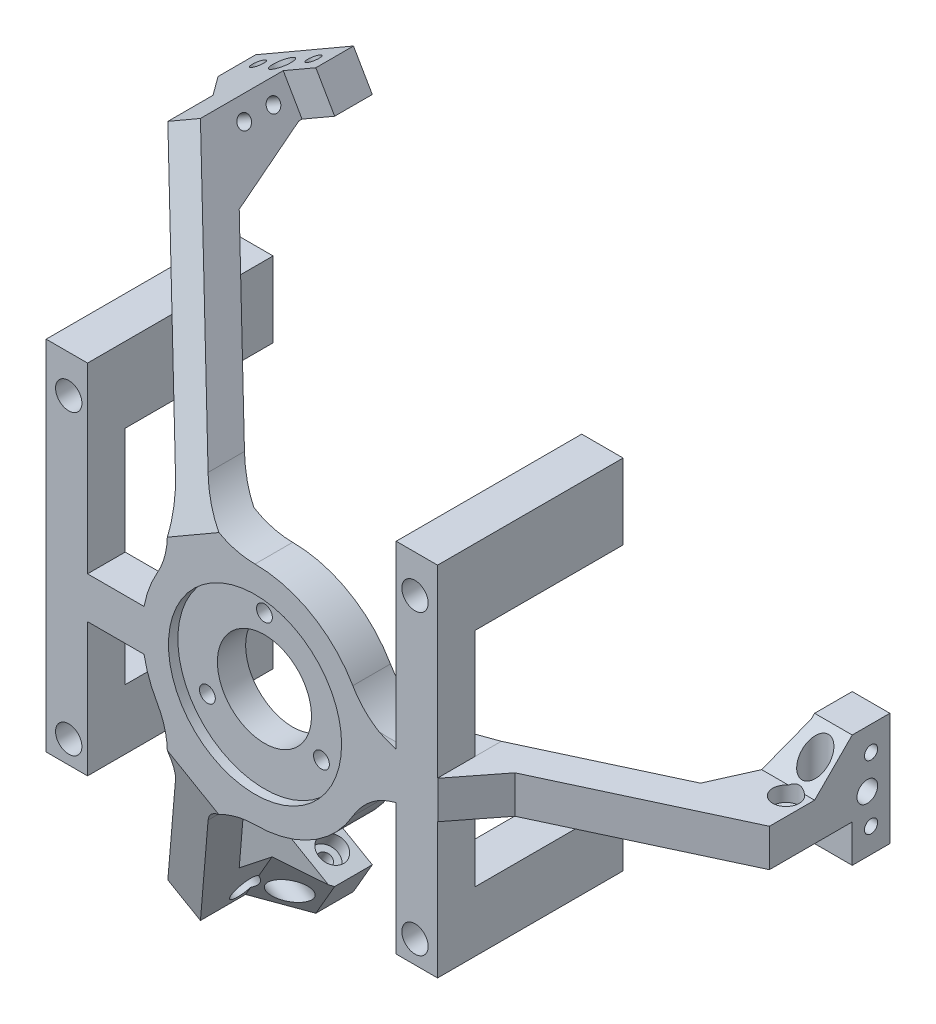
SolidWorks part; units mm, degrees
ref_plane "Plan de face" through (0, 0, 0) normal (0, 0, 1) x (1, 0, 0)
ref_plane "Plan de dessus" through (0, 0, 0) normal (0, 1, 0) x (1, 0, 0)
ref_plane "Plan de droite" through (0, 0, 0) normal (1, 0, 0) x (0, 0, -1)
sketch "Esquisse1" plane through (0, 0, 0) normal (0, 0, 1) x (1, 0, 0)
  line L0 (0, 0) -> (93.67, 0) construction
  line L1 (93.67, 15) -> (103.67, 15)
  line L2 (93.67, 15) -> (93.67, -15)
  line L3 (93.67, -15) -> (103.67, -15)
  line L4 (103.67, 15) -> (103.67, -15)
  line L5 (-33.8446, -88.6206) -> (-59.8254, -73.6206)
  line L6 (-33.8446, -88.6206) -> (-38.8446, -97.2809)
  line L7 (-38.8446, -97.2809) -> (-64.8254, -82.2809)
  line L8 (-59.8254, -73.6206) -> (-64.8254, -82.2809)
  line L9 (-59.8254, 73.6206) -> (-33.8446, 88.6206)
  line L10 (-59.8254, 73.6206) -> (-64.8254, 82.2809)
  line L11 (-64.8254, 82.2809) -> (-38.8446, 97.2809)
  line L12 (-33.8446, 88.6206) -> (-38.8446, 97.2809)
  point P17 (0, 0)
  dimension "D1" = 30
  dimension "D2" = 10
  dimension "D3" = 93.67
  dimension "D4" = 3
extrude "Boss.-Extru.1" add sketch "Esquisse1" along normal blind 10
sketch "Esquisse2" plane through (0, 0, 10) normal (0, 0, 1) x (1, 0, 0)
  line L0 (-57.0272, 86.7831) -> (-46.3532, 92.9458)
  line L1 (-38.8446, 97.2809) -> (-64.8254, 82.2809) construction
  line L2 (93.67, 15) -> (93.67, -15) construction
  line L3 (93.67, 5) -> (103.67, 5)
  line L4 (93.67, 5) -> (93.67, -5)
  line L5 (93.67, -5) -> (103.67, -5)
  line L6 (103.67, 5) -> (103.67, -5)
  line L7 (103.67, -15) -> (103.67, 15) construction
  line L8 (-42.5049, -83.6206) -> (-51.1651, -78.6206)
  line L9 (-42.5049, -83.6206) -> (-47.5049, -92.2809)
  line L10 (-47.5049, -92.2809) -> (-56.1651, -87.2809)
  line L11 (-51.1651, -78.6206) -> (-56.1651, -87.2809)
  line L12 (-51.1651, 78.6206) -> (-42.5049, 83.6206)
  line L13 (-51.1651, 78.6206) -> (-56.1651, 87.2809)
  line L14 (-56.1651, 87.2809) -> (-47.5049, 92.2809)
  line L15 (-42.5049, 83.6206) -> (-47.5049, 92.2809)
  point P12 (93.67, 0)
  point P13 (93.67, 0)
  point P24 (0, 0)
  line M6 (-59.8254, 73.6206) -> (-33.8446, 88.6206)
  dimension "D1" = 3
extrude "Boss.-Extru.2" add sketch "Esquisse2" along normal blind 45 contours L15 L0 L13 M6 | L6 L3 L4 L5 | L8 L11 L10 L9 region at (-49.335, 85.4507, 10) region at (98.67, 0, 10) region at (-49.335, -85.4507, 10)
sketch "Esquisse3" plane through (0, 0, 55) normal (0, 0, 1) x (1, 0, 0)
  line L0 (103.67, 5) -> (103.67, -5) construction
  line L1 (-47.5049, -92.2809) -> (-56.1651, -87.2809) construction
  line L2 (-47.5049, 92.2809) -> (-56.1651, 87.2809) construction
  line L3 (103.67, 5) -> (103.67, -5)
  line L4 (-47.5049, -92.2809) -> (-56.1651, -87.2809)
  line L5 (-47.5049, 92.2809) -> (-56.1651, 87.2809)
  line L6 (-56.1651, -87.2809) -> (-19.1203, -23.1174)
  line L7 (-47.5049, -92.2809) -> (-10.4601, -28.1174)
  line L8 (103.67, -5) -> (29.5804, -5)
  line L9 (103.67, 5) -> (29.5804, 5)
  line L10 (-56.1651, 87.2809) -> (-19.1203, 23.1174)
  line L11 (-47.5049, 92.2809) -> (-10.4601, 28.1174)
  line L12 (-51.1651, -78.6206) -> (-56.1651, -87.2809) construction
  line L13 (-42.5049, -83.6206) -> (-47.5049, -92.2809) construction
  line L14 (93.67, -5) -> (103.67, -5) construction
  line L15 (93.67, 5) -> (103.67, 5) construction
  line L16 (-51.1651, 78.6206) -> (-56.1651, 87.2809) construction
  line L17 (-42.5049, 83.6206) -> (-47.5049, 92.2809) construction
  arc A0 (-19.1203, -23.1174) -> (-19.1203, 23.1174) centre (0, 0) cw
  arc A1 (-10.4601, 28.1174) -> (29.5804, 5) centre (0, 0) cw
  arc A2 (29.5804, -5) -> (-10.4601, -28.1174) centre (0, 0) cw
  dimension "D1" = 30
extrude "Boss.-Extru.3" add sketch "Esquisse3" along normal blind 10
chamfer "Chanfrein1" distance 28 angle 65 3 edges at (93.67, 0, 55) (-46.835, -81.1206, 55) (-46.835, 81.1206, 55) first distance on face at (93.67, 0, 18.75) first distance on face at (-46.835, -81.1206, 18.75) first distance on face at (-46.835, 81.1206, 18.75)
chamfer "Chanfrein2" distance 33 angle 65 3 edges at (-51.835, -89.7809, 65) (-51.835, 89.7809, 65) (103.67, 0, 65) first distance on face at (-51.835, -89.7809, 21.25) first distance on face at (-51.835, 89.7809, 21.25) first distance on face at (103.67, 0, 21.25)
fillet "Congé1" radius 20 6 edges at (29.5804, -5, 60) (-10.4601, -28.1174, 60) (-19.1203, -23.1174, 60) (-19.1203, 23.1174, 60) (29.5804, 5, 60) (-10.4601, 28.1174, 60)
chamfer "Chanfrein3" distance 10 angle 41 3 edges at (-46.835, 81.1206, 27) (-46.835, -81.1206, 27) (93.67, 0, 27) first distance on face at (-28.4061, 49.2008, 44.1871) first distance on face at (-28.4061, -49.2008, 44.1871) first distance on face at (56.8122, 0, 44.1871)
sketch "Esquisse4" plane through (0, 0, 65) normal (0, 0, 1) x (1, 0, 0)
  circle A0 centre (0, 0) radius 12.5
  dimension "D1" = 25
extrude "Enlèv. mat.-Extru.1" cut sketch "Esquisse4" against normal up to next
sketch "Esquisse5" plane through (0, 0, 65) normal (0, 0, 1) x (1, 0, 0)
  circle A0 centre (0, 0) radius 23
  dimension "D1" = 46
extrude "Enlèv. mat.-Extru.2" cut sketch "Esquisse5" against normal blind 2.5
sketch "Esquisse6" plane through (0, 0, 62.5) normal (0, 0, 1) x (1, 0, 0)
  line L0 (0, 17.5) -> (0, 0) construction
  circle A0 centre (0, 17.5) radius 2.1
  circle A1 centre (15.1554, -8.75) radius 2.1
  circle A2 centre (-15.1554, -8.75) radius 2.1
  point P10 (0, 0)
  dimension "D2" = 4.2
  dimension "D1" = 17.5
  dimension "D3" = 3
extrude "Enlèv. mat.-Extru.3" cut sketch "Esquisse6" against normal up to next
sketch "Esquisse7" plane through (0, 0, 55) normal (0, 0, -1) x (-1, 0, 0)
  line L0 (0, 0) -> (44.5, 0) construction
  line L1 (-37.5, -41) -> (-48.5, -41)
  line L2 (-37.5, -41) -> (-37.5, 54)
  line L3 (-37.5, 54) -> (-48.5, 54)
  line L4 (-48.5, -41) -> (-48.5, 54)
  line L5 (55.5, -41) -> (44.5, -41)
  line L6 (44.5, -41) -> (44.5, -5.5)
  line L7 (44.5, -5.5) -> (29.4915, -5.5)
  line L8 (55.5, -41) -> (55.5, 54)
  line L9 (55.5, 54) -> (44.5, 54)
  line L10 (44.5, 54) -> (44.5, 5.5)
  line L11 (44.5, 5.5) -> (29.4915, 5.5)
  line L12 (44.5, -5.5) -> (44.5, 5.5) construction
  arc A0 (25.9808, -15) -> (25.9808, 15) centre (0, 0) ccw construction
  arc A1 (29.4915, -5.5) -> (29.4915, 5.5) centre (0, 0) ccw
  point P7 (-43, 54)
  point P22 (44.5, 0)
  point P28 (50, 54)
  dimension "D1" = 11
  dimension "D2" = 41
  dimension "D3" = 95
  dimension "D4" = 43
  dimension "D5" = 93
extrude "Boss.-Extru.4" add sketch "Esquisse7" along normal blind 39.3 and the other way up to surface (10 mm away) other way up to face at (23, 0, 65)
sketch "Esquisse8" plane through (0, 0, 15.7) normal (0, 0, -1) x (-1, 0, 0)
  line L0 (-48.5, 6.5) -> (55.5, 6.5) construction
  line L1 (-48.5, 54) -> (-48.5, -41) construction
  line L2 (55.5, -41) -> (55.5, 54) construction
  line L3 (49.5, 44) -> (-42.5, 44) construction
  line L4 (3.5, 6.5) -> (3.5, 44) construction
  line L5 (-48.5, -41) -> (-37.5, -41) construction
  circle A0 centre (49.5, 44) radius 1.75
  circle A1 centre (-42.5, 44) radius 1.75
  circle A2 centre (-42.5, -35) radius 1.75
  circle A3 centre (49.5, -35) radius 1.75
  dimension "D4" = 3.5
  dimension "D1" = 92
  dimension "D2" = 79
  dimension "D3" = 6
extrude "Enlèv. mat.-Extru.4" cut sketch "Esquisse8" against normal up to next
sketch "Esquisse9" plane through (0, 0, 65) normal (0, 0, 1) x (1, 0, 0)
  circle A0 centre (42.5, -35) radius 3.5
  circle A1 centre (42.5, 44) radius 3.5
  circle A2 centre (-49.5, -35) radius 3.5
  circle A3 centre (-49.5, 44) radius 3.5
  dimension "D1" = 7
extrude "Enlèv. mat.-Extru.5" cut sketch "Esquisse9" against normal offset from surface (28.3 mm away) 21 up to face at (40.75, -35, 15.7)
sketch "Esquisse10" plane through (0, 0, 15.7) normal (0, 0, -1) x (-1, 0, 0)
  line L6 (55.5, -41) -> (55.5, 54) construction
  line L7 (55.5, -25) -> (29.4915, -25)
  line L8 (55.5, -25) -> (55.5, 34)
  line L9 (55.5, 34) -> (29.4915, 34)
  line L10 (29.4915, -25) -> (29.4915, 34)
  line L11 (49.5, 44) -> (49.5, 34) construction
  line L12 (49.5, -35) -> (49.5, -25) construction
  line L13 (-48.5, 54) -> (-48.5, -41) construction
  line L14 (-48.5, 34) -> (-37.5, 34)
  line L15 (-48.5, 34) -> (-48.5, -25)
  line L16 (-48.5, -25) -> (-37.5, -25)
  line L17 (-37.5, 34) -> (-37.5, -25)
  line L18 (-37.5, -41) -> (-37.5, 54) construction
  dimension "D1" = 10
extrude "Enlèv. mat.-Extru.6" cut sketch "Esquisse10" against normal up to surface (39.3 mm away) up to face at (-2.1, 17.5, 55)
sketch "Esquisse17" plane through (0, 0, 55) normal (0, 0, -1) x (-1, 0, 0)
  line L0 (-37.5, -5.8599) -> (-48.5, -5)
  line L1 (-48.5, -5) -> (-48.5, 5)
  line L2 (-48.5, 5) -> (-37.5, 5.8599)
  line L3 (-37.5, 5.8599) -> (-37.5, -5.8599)
extrude "Boss.-Extru.5" add sketch "Esquisse17" along normal up to surface (6.9369 mm away) contours L3 L0 L1 L2 up to face at (66.5535, 0, 39.6446)
sketch "Esquisse18" plane through (30.7728, 0, 65.9925) normal (0.4226, 0, 0.9063) x (0.9063, 0, -0.4226)
  line L2 (7.4226, -5.8599) -> (7.4226, 5.8599)
  line L3 (2.3485, 7.9167) -> (2.3485, -7.9167)
  line L4 (7.4226, -5.8599) -> (7.4226, 5.8599)
  line L5 (2.3485, 7.9167) -> (2.3485, -7.9167)
  ellipse E2 centre (13.8236, 25) end of major axis (35.8912, 25) minor radius 20 (2.3485, 7.9167) -> (7.4226, 5.8599) ccw
  ellipse E3 centre (13.8236, -25) end of major axis (35.8912, -25) minor radius 20 (7.4226, -5.8599) -> (2.3485, -7.9167) ccw
  ellipse E4 centre (13.8236, 25) end of major axis (35.8912, 25) minor radius 20 (2.3485, 7.9167) -> (7.4226, 5.8599) ccw
  ellipse E5 centre (13.8236, -25) end of major axis (35.8912, -25) minor radius 20 (7.4226, -5.8599) -> (2.3485, -7.9167) ccw
  dimension "D1" = 0
extrude "Boss.-Extru.6" add sketch "Esquisse18" along normal up to surface (2.3661 mm away) up to face at (46, 44, 65)
chamfer "Chanfrein5" distance 10 angle 27 1 edges at (48.5, 0, 57.7262) first distance on face at (76.085, 0, 44.8631)
sketch "Esquisse11" plane through (4.3301, -2.5, 0) normal (0.866, -0.5, 0) x (0, 0, -1)
  line L0 (-10.8702, -93.67) -> (-10, -93.67) construction
  line L1 (-10, -93.67) -> (-10, -103.67) construction
  circle A0 centre (-15, -98.86) radius 1.75
  circle A1 centre (-22.78, -98.86) radius 1.75
  dimension "D4" = 3.5
  dimension "D1" = 5.19
  dimension "D2" = 5
  dimension "D3" = 7.78
extrude "Enlèv. mat.-Extru.7" cut sketch "Esquisse11" against normal up to next
sketch "Esquisse12" plane through (4.3301, -2.5, 0) normal (0.866, -0.5, 0) x (0, 0, -1)
  circle A0 centre (-15, -98.86) radius 3.5
  circle A1 centre (-22.78, -98.86) radius 3.5
  dimension "D1" = 7
extrude "Enlèv. mat.-Extru.8" cut sketch "Esquisse12" against normal blind 4
sketch "Esquisse13" plane through (-46.835, -81.1206, 0) normal (0.5, 0.866, 0) x (0.866, -0.5, 0)
  line L0 (-15, -10) -> (-15, 0) construction
  line L1 (-15, -5) -> (-8.5, -5) construction
  line L2 (15, -5) -> (8.5, -5) construction
  line L3 (15, -10) -> (15, 0) construction
  circle A0 centre (-8.5, -5) radius 1.75
  circle A1 centre (8.5, -5) radius 1.75
  dimension "D2" = 3.5
  dimension "D1" = 6.5
extrude "Enlèv. mat.-Extru.9" cut sketch "Esquisse13" against normal up to next
sketch "Esquisse14" plane through (-46.835, -81.1206, 0) normal (0.5, 0.866, 0) x (0.866, -0.5, 0)
  circle A0 centre (-8.5, -5) radius 3.5
  circle A1 centre (8.5, -5) radius 3.5
  dimension "D1" = 7
extrude "Enlèv. mat.-Extru.10" cut sketch "Esquisse14" against normal blind 4
sketch "Esquisse15" plane through (-46.835, -81.1206, 0) normal (0.5, 0.866, 0) x (0.866, -0.5, 0)
  line L0 (15, 0) -> (-15, 0) construction
  line L1 (-15, -10) -> (-15, 0) construction
  circle A0 centre (0, -6) radius 2.75
  point P5 (0, 0)
  point P8 (-15, -5)
  dimension "D1" = 5.5
  dimension "D2" = 1
extrude "Enlèv. mat.-Extru.11" cut sketch "Esquisse15" against normal up to next
pattern_circular "Répétition circulaire1" count 3 over 360 about axis through (0, 0, -0.001) along (0, 0, 1) of "Enlèv. mat.-Extru.7", "Enlèv. mat.-Extru.11", "Enlèv. mat.-Extru.10", "Enlèv. mat.-Extru.9", "Enlèv. mat.-Extru.8" reverse direction yes
chamfer "Chanfrein4" distance 10 angle 45 3 edges at (-53.6651, 82.9507, 10) (98.67, 5, 10) (-45.0049, -87.9507, 10)
